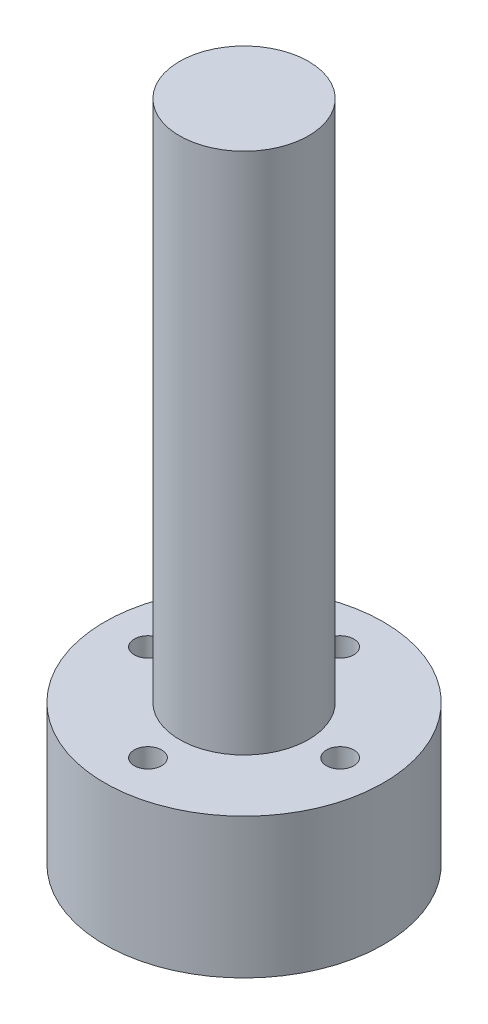
SolidWorks part; units mm, degrees
ref_plane "Front Plane" through (0, 0, 0) normal (0, 0, 1) x (1, 0, 0)
ref_plane "Top Plane" through (0, 0, 0) normal (0, 1, 0) x (1, 0, 0)
ref_plane "Right Plane" through (0, 0, 0) normal (1, 0, 0) x (0, 0, -1)
sketch "Sketch1" plane through (0, 0, 0) normal (0, 1, 0) x (1, 0, 0)
  circle A0 centre (0, 0) radius 10.16
  circle A1 centre (7, 0) radius 1
  circle A2 centre (0, -7) radius 1
  circle A3 centre (-7, 0) radius 1
  circle A4 centre (0, 7) radius 1
  point P14 (0, 0)
  dimension "D1" = 20.32
  dimension "D2" = 2
  dimension "D3" = 7
  dimension "D4" = 4
extrude "Boss-Extrude1" add sketch "Sketch1" along normal blind 19.05
sketch "Sketch2" plane through (0, 19.05, 0) normal (0, 1, 0) x (1, 0, 0)
  circle A0 centre (0, 0) radius 4.699
  dimension "D1" = 9.398
extrude "Boss-Extrude2" add sketch "Sketch2" along normal blind 38.1
sketch "Sketch3" plane through (0, 0, 0) normal (0, 1, 0) x (1, 0, 0)
  circle A0 centre (0, 0) radius 3.429
  dimension "D1" = 6.858
sketch "Sketch4" plane through (0, 0, 0) normal (0, -1, 0) x (1, 0, 0)
  circle A1 centre (0, 0) radius 10.16
  circle A2 centre (0, 0) radius 10.16
  dimension "D1" = 0
extrude "Cut-Extrude2" cut sketch "Sketch4" against normal blind 8.842
extrude "Cut-Extrude3" cut sketch "Sketch3" along normal blind 3.175 from surface starting at face at (7, 8.842, -1)
sketch "Sketch5" plane through (0, 0, 0) normal (0, 0, 1) x (1, 0, 0)
  line L0 (4.699, 57.15) -> (-4.699, 57.15) construction
  circle A0 centre (0, 47.625) radius 1.727
  dimension "D1" = 3.454
  dimension "D2" = 9.525
equation "\"D3@Sketch1\"=7MM"
equation "\"D2@Sketch1\"=2MM"
equation "\"tightTol\"= 0.005in"
equation "\"normTol\"= 0.01in"
equation "\"looseTol\"= 0.02in"
equation "\"D1@Sketch2\"=0.375000-\"tightTol\""
equation "\"D1@Sketch3\"=1/4+\"looseTol\""
equation "\"D1@Cut-Extrude2\"= 15.7mm - 0.25 - \"looseTol\""
equation "\"D1@Sketch5\"=3.2mm+\"normTol\""
